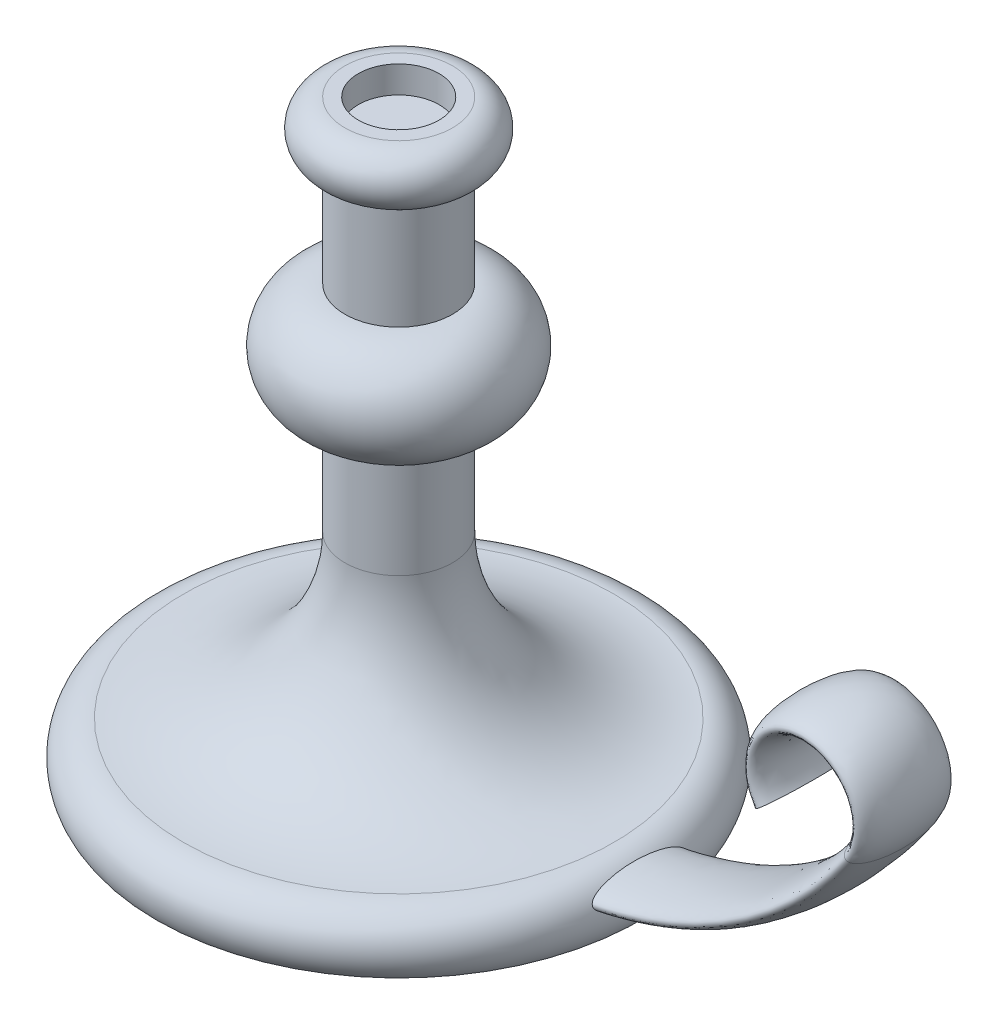
SolidWorks part; units mm, degrees
ref_plane "Front Plane" through (0, 0, 0) normal (0, 0, 1) x (1, 0, 0)
ref_plane "Top Plane" through (0, 0, 0) normal (0, 1, 0) x (1, 0, 0)
ref_plane "Right Plane" through (0, 0, 0) normal (1, 0, 0) x (0, 0, -1)
sketch "Sketch1" plane through (0, 0, 0) normal (0, 0, 1) x (1, 0, 0)
  line L4 (0, 0) -> (90, 0)
  line L5 (-226.2162, 0) -> (285.2027, 0) construction
  line L6 (0, -145.6419) -> (0, 220) construction
  line L7 (0, 0) -> (0, 220)
  line L8 (0, 220) -> (20, 220)
  line L9 (20, 200) -> (20, 160)
  line L10 (20, 120) -> (20, 80)
  arc A0 (20, 220) -> (20, 200) centre (20, 210) cw
  arc A1 (20, 160) -> (20, 120) centre (20, 140) cw
  arc A2 (20, 80) -> (80, 20) centre (80, 80) ccw
  arc A3 (80, 20) -> (90, 0) centre (80, 7.5) cw
  dimension "D4" = 10
  dimension "D6" = 20
  dimension "D8" = 60
  dimension "D9" = 12.5
  dimension "D1" = 90
  dimension "D2" = 220
  dimension "D3" = 20
  dimension "D5" = 40
  dimension "D7" = 80
ref_axis "Axis1" through (0, 0, 0) along (0, 1, 0)
revolve "Revolve1" add sketch "Sketch1" angle 360 about L7
sketch "Sketch2" plane through (0, 0, 0) normal (0, 0, 1) x (1, 0, 0)
  line L0 (0, 0) -> (0, 220) construction
  line L1 (0, 10) -> (60, 10)
  arc A0 (60, 10) -> (183.5921, 75) centre (60, 160) ccw
  arc A1 (183.5921, 75) -> (150.6342, 75) centre (167.1131, 86.3333) ccw
  dimension "D2" = 150
  dimension "D5" = 20
  dimension "D1" = 60
  dimension "D3" = 65
  dimension "D4" = 10
sketch "Sketch5" plane through (0, 0, 0) normal (1, 0, 0) x (0, 0, -1)
  ellipse E0 centre (0, 10) end of major axis (-17.5, 10) minor radius 5
  point P1 (0, 0)
  point P7 (85.8931, 73.0783)
  point P8 (0.752, 17.6665)
  point P9 (0, 10)
  dimension "D1" = 10
  dimension "D2" = 35
sweep "Sweep1" add profiles "Sketch5" path "Sketch2"
sketch "Sketch6" plane through (0, 220, 0) normal (0, 1, 0) x (1, 0, 0)
  circle A0 centre (0, 0) radius 15
  dimension "D1" = 30
extrude "Cut-Extrude1" cut sketch "Sketch6" against normal blind 10
